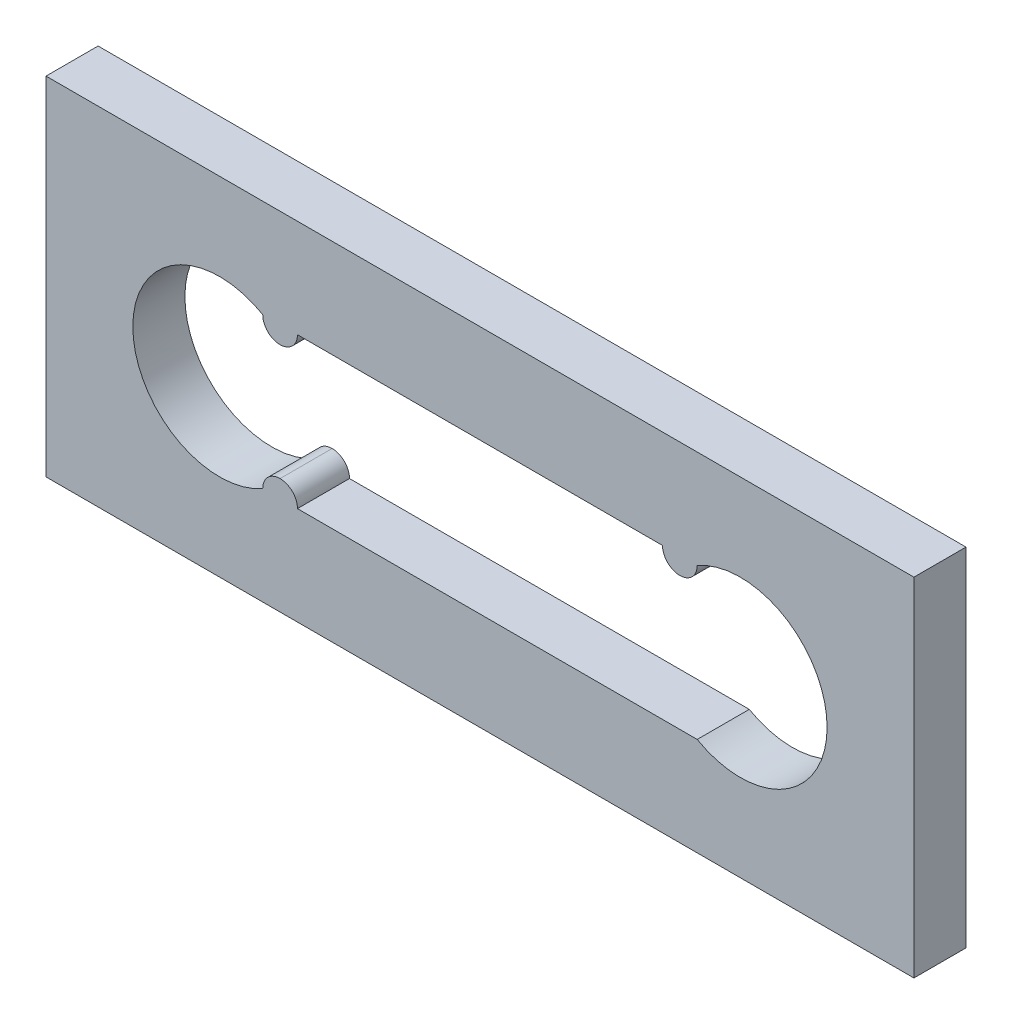
SolidWorks part; units mm, degrees
ref_plane "정면" through (0, 0, 0) normal (0, 0, 1) x (1, 0, 0)
ref_plane "윗면" through (0, 0, 0) normal (0, 1, 0) x (1, 0, 0)
ref_plane "우측면" through (0, 0, 0) normal (1, 0, 0) x (0, 0, -1)
sketch "스케치1" plane through (0, 0, 0) normal (0, 0, 1) x (1, 0, 0)
  line L1 (-25, -10) -> (25, -10)
  line L2 (-25, -10) -> (-25, 10)
  line L3 (-25, 10) -> (25, 10)
  line L4 (25, -10) -> (25, 10)
  line L5 (-25, -10) -> (25, 10) construction
  line L6 (-25, 10) -> (25, -10) construction
  line L7 (-15, -4) -> (15, -4)
  line L8 (-15, -4) -> (-15, 4)
  line L9 (-15, 4) -> (15, 4)
  line L10 (15, -4) -> (15, 4)
  line L11 (-15, -4) -> (15, 4) construction
  line L12 (-15, 4) -> (15, -4) construction
  circle A0 centre (-15, 0) radius 5
  circle A1 centre (15, 0) radius 5
  point P0 (0, 0)
  point P10 (0, 0)
  dimension "D3" = 10
  dimension "D4" = 10
  dimension "D1" = 50
  dimension "D2" = 20
  dimension "D5" = 30
  dimension "D6" = 8
  dimension "D7" = 0
  dimension "D8" = 0
extrude "보스-돌출1" add sketch "스케치1" against normal blind 3 contours L3 L4 L1 L2
sketch "스케치3" plane through (0, 0, 0) normal (0, 0, 1) x (1, 0, 0)
  line L1 (-15, -4.339) -> (15, -4.339)
  line L2 (-15, -4.339) -> (-15, 4.339)
  line L3 (-15, 4.339) -> (15, 4.339)
  line L4 (15, -4.339) -> (15, 4.339)
  line L5 (-15, -4.339) -> (15, 4.339) construction
  line L6 (-15, 4.339) -> (15, -4.339) construction
  circle A0 centre (-15, 0) radius 5
  circle A1 centre (15, 0) radius 5
  point P0 (0, 0)
  dimension "D1" = 10
  dimension "D2" = 10
  dimension "D3" = 30
extrude "컷-돌출1" cut sketch "스케치3" against normal blind 3 contours A0 | L1 L4 L3 L2 | A1
sketch "스케치4" plane through (0, 4.339, 0) normal (0, -1, 0) x (1, 0, 0)
  line L0 (-12.5155, -3) -> (12.5155, -3) construction
  line L1 (-12.5155, 0) -> (-10.5155, 0)
  line L2 (-12.5155, 0) -> (-12.5155, -3)
  line L3 (-12.5155, -3) -> (-10.5155, -3)
  line L4 (-10.5155, 0) -> (-10.5155, -3)
  line L6 (12.5155, 0) -> (10.5155, 0)
  line L7 (12.5155, 0) -> (12.5155, -3)
  line L8 (12.5155, -3) -> (10.5155, -3)
  line L9 (10.5155, 0) -> (10.5155, -3)
  dimension "D1" = 2
  dimension "D2" = 2
extrude "보스-돌출2" add sketch "스케치4" along normal blind 1
fillet "필렛1" radius 1 4 edges at (12.5155, 3.339, -1.5) (10.5155, 3.339, -1.5) (-10.5155, 3.339, -1.5) (-12.5155, 3.339, -1.5)
sketch "스케치5" plane through (0, -4.339, 0) normal (0, 1, 0) x (1, 0, 0)
  line L0 (-12.5155, 3) -> (12.5155, 3) construction
  line L1 (-12.5155, 0) -> (-10.5155, 0)
  line L2 (-12.5155, 0) -> (-12.5155, 3)
  line L3 (-12.5155, 3) -> (-10.5155, 3)
  line L4 (-10.5155, 0) -> (-10.5155, 3)
  dimension "D1" = 2
extrude "보스-돌출3" add sketch "스케치5" along normal blind 1
fillet "필렛2" radius 1 2 edges at (-12.5155, -3.339, -1.5) (-10.5155, -3.339, -1.5)
